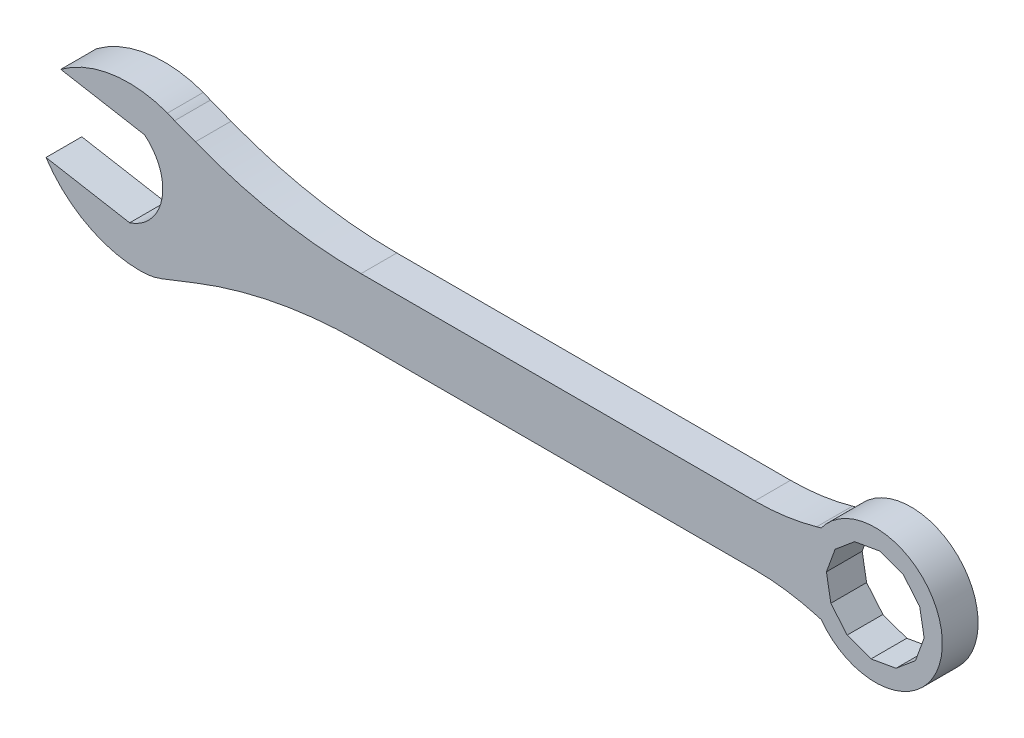
SolidWorks part; units mm, degrees
material "주조 탄소강"
ref_plane "Front Plane" through (0, 0, 0) normal (0, 0, 1) x (1, 0, 0)
ref_plane "Top Plane" through (0, 0, 0) normal (0, 1, 0) x (1, 0, 0)
ref_plane "Right Plane" through (0, 0, 0) normal (1, 0, 0) x (0, 0, -1)
ref_axis "x" through (-7.1105, 0, 0) along (1, 0, 0)
ref_axis "y" through (0, 56.4538, 0) along (0, -1, 0)
ref_axis "z" through (0, 0, -89.2869) along (0, 0, 1)
sketch "Sketch1" plane through (0, 0, 0) normal (0, 0, -1) x (1, 0, 0)
  line L0 (-20.361, 6.0564) -> (-1.6497, 9.3557)
  line L1 (1.6497, -9.3557) -> (-17.0617, -12.655)
  line L2 (0, 0) -> (-9.5, 0) construction
  line L3 (0, 0) -> (-9.3557, -1.6497) construction
  line L4 (1.6497, -9.3557) -> (-1.6497, 9.3557)
  arc A0 (1.6497, -9.3557) -> (-1.6497, 9.3557) centre (-5.0334, -0.8875) ccw
  arc A1 (11.7494, 11.3459) -> (14.9214, -6.6431) centre (-10.0056, -1.7643) cw
  arc A2 (14.9214, -6.6431) -> (6.8173, -16.132) centre (2.4579, -4.2037) cw
  arc A3 (6.8173, -16.132) -> (-17.0617, -12.655) centre (-1.9015, 7.7247) cw
  arc A4 (11.7494, 11.3459) -> (0.8887, 17.4908) centre (0.8719, 4.7908) ccw
  arc A5 (-20.361, 6.0564) -> (0.8887, 17.4908) centre (0.8551, -7.9092) cw
  dimension "D3" = 10.16
  dimension "D5" = 25.4
  dimension "D6" = 12.7
  dimension "D7" = 25.4
  dimension "D8" = 25.4
  dimension "D4" = 19
  dimension "D10" = 12.7
  dimension "D11" = 34.925
  dimension "D1" = 10
  dimension "D2" = 5.111
  dimension "D9" = 19
  dimension "D12" = 9.5
  dimension "D13" = 9.5
extrude "Boss-Extrude1" add sketch "Sketch1" along normal mid plane 8 contours L0 A5 A4 A1 A2 A3 L1 A0 region at (-10.9431, -14.0165, 0)
sketch "Sketch2" plane through (0, 0, 0) normal (0, 0, -1) x (1, 0, 0)
  line L0 (0, 0) -> (110.2756, 0) construction
  line L1 (50.0912, 6.6675) -> (138.1458, 6.6675)
  line L2 (151.994, 8.5915) -> (164.2536, 12.065)
  line L3 (164.2536, 12.065) -> (164.2536, -12.065)
  line L4 (13.0376, 13.6652) -> (5.5036, 16.6161)
  line L5 (151.994, -8.5915) -> (164.2536, -12.065)
  line L6 (50.0912, -6.6675) -> (138.1458, -6.6675)
  line L7 (13.0376, -13.6652) -> (5.4743, -16.5403)
  arc A0 (13.0376, 13.6652) -> (50.0912, 6.6675) centre (50.0912, 108.2675) ccw
  arc A1 (151.994, 8.5915) -> (138.1458, 6.6675) centre (138.1458, 57.4675) cw
  arc A2 (151.994, -8.5915) -> (138.1458, -6.6675) centre (138.1458, -57.4675) ccw
  arc A4 (13.0376, -13.6652) -> (50.0912, -6.6675) centre (50.0912, -108.2675) cw
  arc A7 (6.8173, -16.132) -> (14.9214, -6.6431) centre (2.4579, -4.2037) ccw construction
  arc A9 (11.7494, 11.3459) -> (0.8887, 17.4908) centre (0.8719, 4.7908) ccw construction
  arc A10 (14.9214, -6.6431) -> (11.7494, 11.3459) centre (-10.0056, -1.7643) ccw construction
  arc A23 (6.8173, -16.132) -> (14.9214, -6.6431) centre (2.4579, -4.2037) ccw
  arc A25 (14.9214, -6.6431) -> (11.7494, 11.3459) centre (-10.0056, -1.7643) ccw
  arc A27 (11.7494, 11.3459) -> (0.8887, 17.4908) centre (0.8719, 4.7908) ccw
  point P7 (30.9036, 6.6675)
  point P22 (164.2536, 0)
  point P26 (145.2036, 6.6675)
  dimension "D3" = 101.6
  dimension "D5" = 50.8
  dimension "D1" = 25.4
  dimension "D2" = 158.75
  dimension "D4" = 24.13
  dimension "D6" = 19.05
  dimension "D7" = 13.335
extrude "Boss-Extrude2" add sketch "Sketch2" along normal mid plane 8 contours A27 A25 A23 L7 A4 L6 A2 L5 L3 L2 A1 L1 A0 L4 | A25 A27 L4 A0 L1 A1 L2 L3 L5 A2 L6 A4 L7 A23 | L6 A2 L5 L3 L2 A1 L1 A0 L4 A27 A25 A23 L7 A4 region at (87.5187, -0.0542, 0)
ref_plane "Plane1" through (0, 0, -4) normal (0, 0, 1) x (1, 0, 0)
ref_plane "Plane2" through (0, 0, 0) normal (0, 0, 1) x (1, 0, 0)
sketch "Sketch3" plane through (0, 0, 0) normal (0, 0, 1) x (1, 0, 0)
  line L0 (165.1, 0) -> (0, 0) construction
  circle A0 centre (165.1, 0) radius 15
  dimension "D2" = 30
  dimension "D1" = 165.1
extrude "Boss-Extrude3" add sketch "Sketch3" along normal mid plane 8
sketch "Sketch4" plane through (0, 0, 4) normal (0, 0, 1) x (0.9848, 0.1736, 0)
  line L1 (154.8352, -36.4259) -> (159.7526, -39.265)
  line L2 (159.7526, -39.265) -> (165.4309, -39.265)
  line L3 (165.4309, -39.265) -> (170.3484, -36.4259)
  line L4 (170.3484, -36.4259) -> (173.1875, -31.5084)
  line L5 (173.1875, -31.5084) -> (173.1875, -25.8302)
  line L6 (173.1875, -25.8302) -> (170.3484, -20.9127)
  line L7 (170.3484, -20.9127) -> (165.4309, -18.0736)
  line L8 (165.4309, -18.0736) -> (159.7526, -18.0736)
  line L9 (159.7526, -18.0736) -> (154.8352, -20.9127)
  line L10 (154.8352, -20.9127) -> (151.996, -25.8302)
  line L11 (151.996, -25.8302) -> (151.996, -31.5084)
  line L12 (151.996, -31.5084) -> (154.8352, -36.4259)
  circle A0 centre (162.5918, -28.6693) radius 15 construction
  circle A1 centre (162.5918, -28.6693) radius 10.9695 construction
  dimension "D1" = 21.939
extrude "Cut-Extrude1" cut sketch "Sketch4" against normal through all
sketch "Sketch5" plane through (0, 0, 4) normal (0, 0, 1) x (1, 0, 0)
  line L0 (31.75, 0) -> (133.35, 0) construction
  line L1 (31.75, 4.1275) -> (133.35, 4.1275)
  line L2 (31.75, -4.1275) -> (133.35, -4.1275)
  arc A0 (31.75, 4.1275) -> (31.75, -4.1275) centre (31.75, 0) ccw
  arc A1 (133.35, -4.1275) -> (133.35, 4.1275) centre (133.35, 0) ccw
  point P2 (82.55, 0)
  dimension "D1" = 101.6
  dimension "D2" = 8.255
  dimension "D3" = 31.75
extrude "Cut-Extrude2" [suppressed] cut sketch "Sketch5" against normal blind 0.762
mirror "Mirror1" [suppressed] about plane through (0, 0, 0) normal (0, 0, 1)
fillet "Fillet2" [suppressed] radius 0.762
fillet "Fillet3" [suppressed] radius 1.27
fillet "Fillet4" [suppressed] radius 0.381 tangent propagation no
sketch "Sketch6" [suppressed] plane through (0, 0, 1.4605) normal (0, 0, 1) x (1, 0, 0)
  text T0 "5/8"
  dimension "D1" = 33.655
  dimension "D2" = 1.905
extrude "Boss-Extrude4" [suppressed] add sketch "Sketch6" along normal blind 0.381
sketch "Sketch7" [suppressed] plane through (0, 0, 1.4605) normal (0, 0, 1) x (1, 0, 0)
  text T0 "SPANNER" font "Century Gothic" height in points 14
  dimension "D1" = 69.85
  dimension "D2" = 1.905
extrude "Boss-Extrude5" [suppressed] add sketch "Sketch7" along normal blind 0.381
